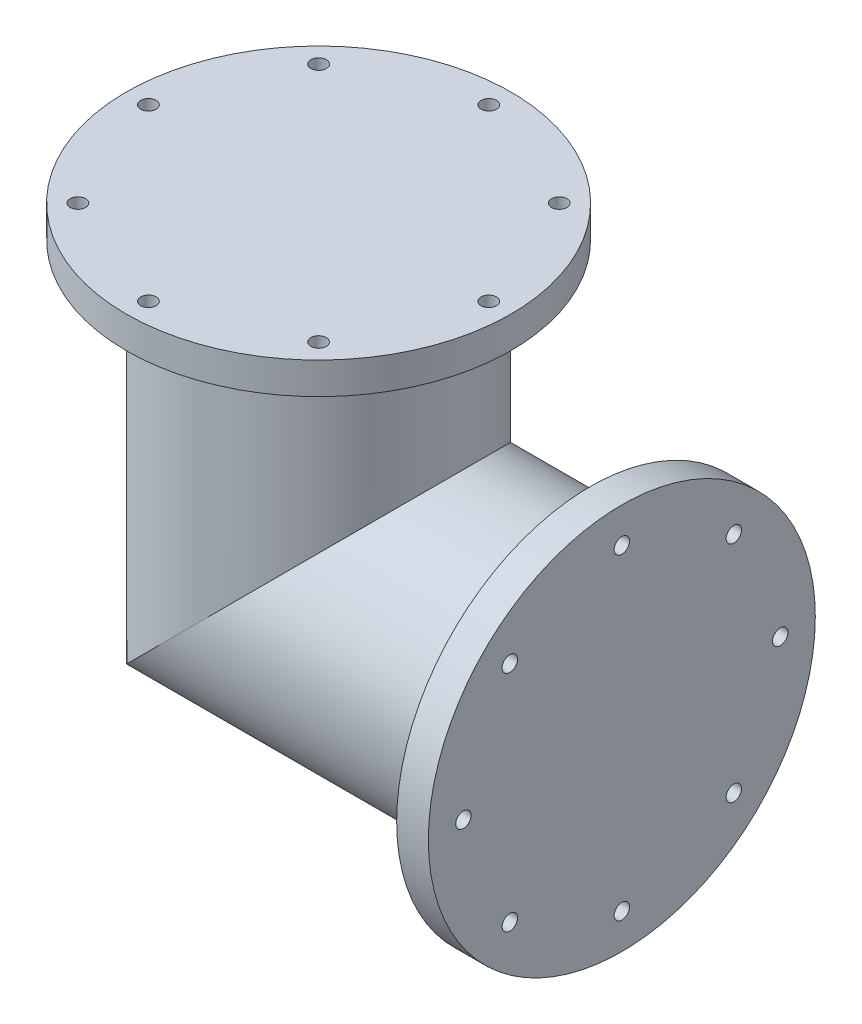
SolidWorks part; units mm, degrees
other "Elemento de detalle1"
other "Carpeta de soldadura"
other "Cordón de soldadura1"
material "7075-O (SS)"
ref_plane "Front" through (0, 0, 0) normal (0, 0, 1) x (1, 0, 0)
ref_plane "Top" through (0, 0, 0) normal (0, 1, 0) x (1, 0, 0)
ref_plane "Right" through (0, 0, 0) normal (1, 0, 0) x (0, 0, -1)
sketch "Croquis1" plane through (0, 0, 0) normal (1, 0, 0) x (0, 0, -1)
  circle A0 centre (0, 0) radius 42.75
  dimension "D1" = 85.5
extrude "Saliente-Extruir1" add sketch "Croquis1" along normal mid plane 7
sketch "Croquis2" plane through (0, 0, 0) normal (0, 0, 1) x (1, 0, 0)
  line L0 (-13.5, -50) -> (-63.5, 0) construction
  line L2 (3.85, 0) -> (-3.85, 0) construction
  line L4 (-3.5, 42.75) -> (-3.5, -42.75) construction
  dimension "D1" = 45
  dimension "D2" = 10
  dimension "D3" = 50
ref_plane "Plano1" through (-63.5, 0, 0) normal (-0.7071, 0.7071, 0) x (0, 0, 1)
sketch "Croquis3" plane through (-3.5, 0, 0) normal (-1, 0, 0) x (0, 0, 1)
  circle A0 centre (0, 0) radius 30
  circle A1 centre (0, 0) radius 25
  dimension "D1" = 60
  dimension "D2" = 50
extrude "Saliente-Extruir2" add sketch "Croquis3" along normal up to surface (60 mm away) up to plane "Plano1"
ref_plane "Plano2" through (0, 60, 0) normal (0, 1, 0) x (1, 0, 0)
sketch "Croquis4" plane through (0, 60, 0) normal (0, 1, 0) x (1, 0, 0)
  circle A0 centre (-63.5, 0) radius 30 construction
  circle A1 centre (-63.5, 0) radius 30
  circle A2 centre (-63.5, 0) radius 25 construction
  circle A3 centre (-63.5, 0) radius 25
extrude "Saliente-Extruir3" add sketch "Croquis4" against normal up to surface (60 mm away) separate body up to face at (-38.5, 25, 0)
hole_wizard "Refrentado para tornillo con cabeza troncocónica de M31" positions "Croquis5" profile "Croquis7" counterbore size "M3" standard "Ansi Metric" end condition up to next
sketch "Croquis5" plane through (-3.5, 0, 0) normal (-1, 0, 0) x (0, 0, 1)
  line L0 (0, -47.025) -> (0, 47.025) construction
  line L1 (47.025, 0) -> (-47.025, 0) construction
  point P0 (0, 35)
  point P12 (24.7487, 24.7487)
  point P13 (35, 0)
  point P14 (24.7487, -24.7487)
  point P15 (0, -35)
  point P16 (-24.7487, -24.7487)
  point P17 (-35, 0)
  point P18 (-24.7487, 24.7487)
  dimension "D1" = 35
  dimension "D2" = 8
sketch "Croquis7" plane through (-3.5, 35, 0) normal (0, 1, 0) x (0, 0, 1)
  line L0 (0, 0) -> (0, 7)
  line L1 (0, 7) -> (1.7, 7)
  line L3 (1.7, 7) -> (1.7, 2.4)
  line L4 (1.7, 2.4) -> (3.5, 2.4)
  line L5 (3.5, 2.4) -> (3.5, 0)
  line L7 (3.5, 0) -> (0, 0)
  line L11 (0, -6.35) -> (0, 107.95) construction
  dimension "Diámetro de taladro hasta el siguiente" = 3.4
  dimension "Profundidad de taladro hasta el siguiente" = 7
  dimension "Diámetro de refrentado" = 7
  dimension "Profundidad de refrentado" = 2.4
sketch "Croquis8" plane through (0, 60, 0) normal (0, 1, 0) x (1, 0, 0)
  line L0 (-60.3625, 0) -> (60.3625, 0) construction
  circle A0 centre (-63.5, 0) radius 42.5
  circle A1 centre (-63.5, 0) radius 25 construction
  dimension "D1" = 85
extrude "Saliente-Extruir4" add sketch "Croquis8" along normal blind 7
hole_wizard "Refrentado para tornillo con cabeza troncocónica de M32" positions "Croquis9" profile "Croquis10" counterbore size "M3" standard "Ansi Metric" end condition up to next
sketch "Croquis9" plane through (0, 60, 0) normal (0, -1, 0) x (-1, 0, 0)
  line L0 (63.5, 0) -> (63.5, -37.6) construction
  line L1 (-60.225, 0) -> (60.225, 0) construction
  line L4 (63.5, 0) -> (63.5, 37.6) construction
  circle A0 centre (63.5, 0) radius 30 construction
  point P0 (63.5, -37.6)
  point P24 (36.9128, -26.5872)
  point P25 (25.9, 0)
  point P26 (36.9128, 26.5872)
  point P27 (63.5, 37.6)
  point P28 (90.0872, 26.5872)
  point P29 (101.1, 0)
  point P30 (90.0872, -26.5872)
  dimension "D1" = 37.6
  dimension "D3" = 8
sketch "Croquis10" plane through (-63.5, 60, 37.6) normal (1, 0, 0) x (0, 0, -1)
  line L0 (0, 0) -> (0, 7.001)
  line L1 (0, 7.001) -> (1.7, 7.001)
  line L3 (1.7, 7.001) -> (1.7, 2.4)
  line L4 (1.7, 2.4) -> (3.5, 2.4)
  line L5 (3.5, 2.4) -> (3.5, 0)
  line L7 (3.5, 0) -> (0, 0)
  line L11 (0, -6.35) -> (0, 107.95) construction
  dimension "Diámetro de taladro hasta el siguiente" = 3.4
  dimension "Profundidad de taladro hasta el siguiente" = 7.001
  dimension "Diámetro de refrentado" = 7
  dimension "Profundidad de refrentado" = 2.4
